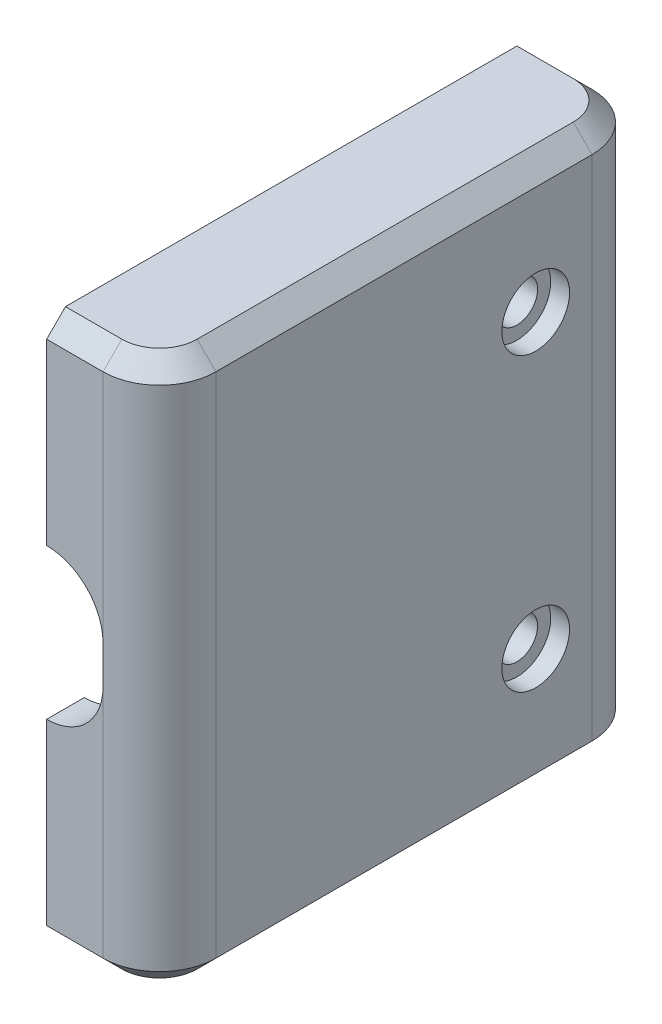
SolidWorks part; units mm, degrees
ref_plane "Спереди" through (0, 0, 0) normal (0, 0, 1) x (1, 0, 0)
ref_plane "Сверху" through (0, 0, 0) normal (0, 1, 0) x (1, 0, 0)
ref_plane "Справа" through (0, 0, 0) normal (1, 0, 0) x (0, 0, -1)
sketch "Эскиз1" plane through (0, 0, 0) normal (1, 0, 0) x (0, 0, -1)
  line L1 (-13, 14.5) -> (13, 14.5)
  line L2 (-13, 14.5) -> (-13, -14.5)
  line L3 (-13, -14.5) -> (13, -14.5)
  line L4 (13, 14.5) -> (13, -14.5)
  line L5 (-13, 14.5) -> (13, -14.5) construction
  line L6 (-13, -14.5) -> (13, 14.5) construction
  point P0 (0, 0)
  dimension "D1" = 26
  dimension "D2" = 29
extrude "Бобышка-Вытянуть1" add sketch "Эскиз1" along normal blind 6
sketch "Эскиз2" plane through (0, 0, 0) normal (-1, 0, 0) x (0, 0, 1)
  line L0 (-13, 0) -> (13, 0) construction
  line L1 (-13, -14.5) -> (-13, 14.5) construction
  line L2 (13, 14.5) -> (13, -14.5) construction
  circle A0 centre (-7, 7.75) radius 1.1
  circle A1 centre (-7, -7.75) radius 1.1
  dimension "D2" = 2.2
  dimension "D1" = 6
  dimension "D3" = 15.5
extrude "Вырез-Вытянуть1" cut sketch "Эскиз2" against normal through all
sketch "Эскиз4" plane through (0, 0, 0) normal (-1, 0, 0) x (0, 0, 1)
  line L0 (-13, 14.5) -> (13, 14.5) construction
  line L1 (5, 11.5) -> (-11, 11.5)
  line L2 (5, 11.5) -> (5, -11.5)
  line L3 (5, -11.5) -> (-11, -11.5)
  line L4 (-11, 11.5) -> (-11, -11.5)
  line L5 (5, 11.5) -> (-11, -11.5) construction
  line L6 (5, -11.5) -> (-11, 11.5) construction
  line L7 (-13, -14.5) -> (-13, 14.5) construction
  line L8 (13, 14.5) -> (13, -14.5) construction
  point P0 (-3, 0)
  dimension "D1" = 3
  dimension "D2" = 2
  dimension "D3" = 8
extrude "Вырез-Вытянуть3" cut sketch "Эскиз4" against normal blind 2
sketch "Эскиз5" plane through (2, 0, 0) normal (-1, 0, 0) x (0, 0, 1)
  line L0 (-11, -3.5) -> (-11, 3.5)
  line L1 (-11, 11.5) -> (-11, -11.5) construction
  line L2 (-11, 3.5) -> (-6, 3.5)
  line L3 (-6, 3.5) -> (-6, 10.5)
  line L4 (-6, 10.5) -> (5, 10.5)
  line L5 (5, -11.5) -> (5, 11.5) construction
  line L6 (5, 10.5) -> (5, -10.5)
  line L7 (-11, 0) -> (5, 0) construction
  line L8 (-11, 11.5) -> (-11, -11.5) construction
  line L11 (-6, -10.5) -> (5, -10.5)
  line L12 (-6, -3.5) -> (-6, -10.5)
  line L13 (-11, -3.5) -> (-6, -3.5)
  dimension "D1" = 5
  dimension "D2" = 7
  dimension "D3" = 21
extrude "Вырез-Вытянуть4" cut sketch "Эскиз5" against normal blind 1.5
fillet "Скругление1" radius 1 8 edges at (2.75, 3.5, -6) (2.75, 3.5, -11) (2.75, -3.5, -11) (2.75, -3.5, -6) (2.75, -8.2083, -6) (2.75, -7.2917, -6) (2.75, 7.2917, -6) (2.75, 8.2083, -6)
sketch "Эскиз6" plane through (6, 0, 0) normal (1, 0, 0) x (0, 0, -1)
  circle A0 centre (7, 7.75) radius 1.8
  circle A1 centre (7, -7.75) radius 1.8
  dimension "D1" = 3.6
  dimension "D2" = 3.6
extrude "Вырез-Вытянуть5" cut sketch "Эскиз6" against normal blind 1
fillet "Скругление3" radius 3 2 edges at (6, 0, 13) (6, 0, -13)
sketch "Эскиз8" plane through (0, 0, 0) normal (-1, 0, 0) x (0, 0, 1)
  line L0 (5, -11.5) -> (5, 11.5) construction
  line L1 (11, 10.5) -> (5, 10.5)
  line L2 (11, 10.5) -> (11, -10.5)
  line L3 (11, -10.5) -> (5, -10.5)
  line L4 (5, 10.5) -> (5, -10.5)
  line L5 (11, 10.5) -> (5, -10.5) construction
  line L6 (11, -10.5) -> (5, 10.5) construction
  line L7 (13, 14.5) -> (13, -14.5) construction
  line L8 (5, 10.5) -> (-6, 10.5) construction
  line L9 (-6, -10.5) -> (5, -10.5) construction
  point P0 (8, 0)
  dimension "D1" = 2
extrude "Вырез-Вытянуть6" cut sketch "Эскиз8" against normal up to surface (3.5 mm away) up to face at (3.5, 0, -5.9486)
fillet "Скругление2" radius 1 8 edges at (1, -11.5, -11) (1, -11.5, 5) (2.75, -10.5, -6) (1, 11.5, -11) (1, 11.5, 5) (2.75, 10.5, -6) (1.75, -10.5, 11) (1.75, 10.5, 11)
fillet "Скругление4" radius 1 2 edges at (1, -10.5, 5) (1, 10.5, 5)
sketch "Эскиз9" plane through (0, 0, 11) normal (0, 0, -1) x (-1, 0, 0)
  line L1 (3, 4) -> (-3, 4)
  line L2 (3, 4) -> (3, -4)
  line L3 (3, -4) -> (-3, -4)
  line L4 (-3, 4) -> (-3, -4)
  line L5 (3, 4) -> (-3, -4) construction
  line L6 (3, -4) -> (-3, 4) construction
  line L8 (0, -14.5) -> (0, 14.5) construction
  point P0 (0, 0)
  dimension "D1" = 8
  dimension "D2" = 3
extrude "Вырез-Вытянуть7" cut sketch "Эскиз9" against normal up to next
fillet "Скругление5" radius 3 2 edges at (3, -4, 12) (3, 4, 12)
chamfer "Фаска2" distance 1 angle 45 10 edges at (1.5, 14.5, -13) (1.5, 14.5, 13) (5.1213, 14.5, -12.1213) (5.1213, 14.5, 12.1213) (6, 14.5, 0) (1.5, -14.5, 13) (1.5, -14.5, -13) (5.1213, -14.5, 12.1213) (5.1213, -14.5, -12.1213) (6, -14.5, 0)
equation "\"motor_diameter\"= 30"
equation "\"mm_diameter\"= IIF ( \"motor_diameter\" < 34 , 41 , \"motor_diameter\" + 8 )"
equation "\"upper_shafts_diameter\"= 5"
equation "\"upper_shats_length\"= 180"
equation "\"upper_bearing_d1\"= 10"
equation "\"upper_bearing_d2\"= 5"
equation "\"upper_bearing_h\"= 15"
equation "\"lower_shafts_diameter\"= 5"
equation "\"lower_shafts_length\"= 180"
equation "\"lower_bearing_d1\"= 10"
equation "\"lower_bearing_d2\"= 5"
equation "\"lower_bearing_h\"= 15"
equation "\"print_offset\"= 0.2"
equation "\"bh_screws_d\"= 2"
equation "\"bh_screws_h\"= 20"
equation "\"bh_screws_hh_d\"= 3.4"
equation "\"bh_screws_hh_h\"= 2"
equation "\"bh_nut_d\"= 3.8"
equation "\"bh_nut_h\"= 2"
equation "\"motor_screws_d\"= 3"
equation "\"motor_screws_h\"= 16"
equation "\"motor_screws_hh_d\"= 5.5"
equation "\"motor_screws_hh_h\"= 3"
equation "\"plate_hole_distance\"= 25.4"
equation "\"plate_screws_d\"= 6.5"
equation "\"shafts_diameter\"= IIF ( \"mm_diameter\" < 42 , 42 + 8 , \"mm_diameter\" + 8 )"
equation "\"central_hole_diameter\"= 8"
equation "\"bh_thikness\"= 4"
equation "\"ends_screws_d\"= 4"
equation "\"ends_screws_h\"= 16"
equation "\"ends_screws_hh_d\"= 6.7"
equation "\"ends_screws_hh_h\"= 4.1"
equation "\"ends_nut_d\"= 6.8"
equation "\"ends_nut_h\"= 3"
equation "\"system_radius\" = ( \"shafts_diameter\" + 12 + \"bh_thikness\" / 2 ) / 2"
equation "\"encoder_distance\"= \"system_radius\" + 4"
equation "\"tape_position\"= \"encoder_distance\" - 2 + 3.9 + 1.7 / 2"
equation "\"D2@Эскиз1\"=\"upper_bearing_h\"+\"bh_thikness\"*2+6"
equation "\"D2@Эскиз2\"=\"bh_screws_d\"+\"print_offset\""
equation "\"D1@Эскиз6\"=\"bh_screws_hh_d\"+\"print_offset\""
equation "\"D2@Эскиз6\"=\"D1@Эскиз6\""
